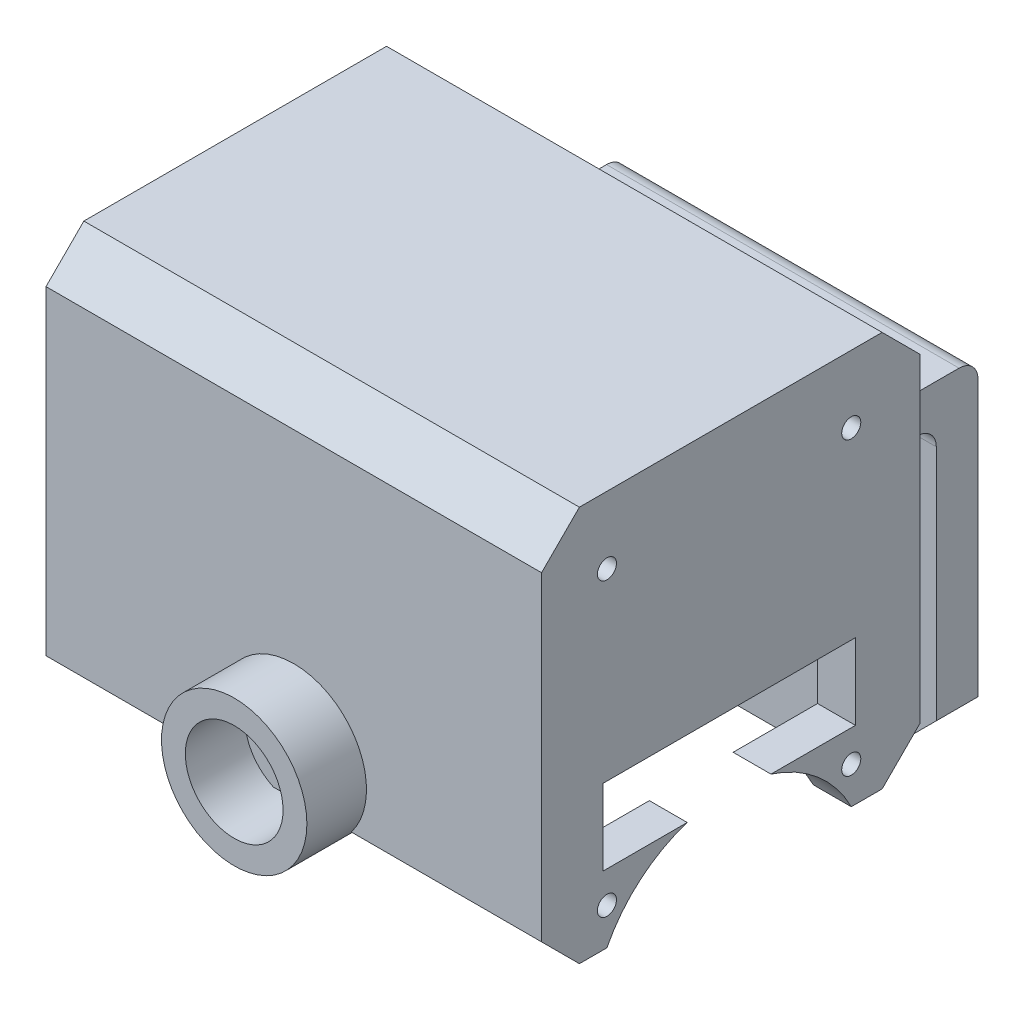
SolidWorks part; units mm, degrees
material "PLA"
ref_plane "Front Plane" through (0, 0, 0) normal (0, 0, 1) x (1, 0, 0)
ref_plane "Top Plane" through (0, 0, 0) normal (0, 1, 0) x (1, 0, 0)
ref_plane "Right Plane" through (0, 0, 0) normal (1, 0, 0) x (0, 0, -1)
sketch "Sketch1" plane through (0, 0, 0) normal (1, 0, 0) x (0, 0, -1)
  line L1 (0, 0) -> (25, 0)
  line L2 (0, 0) -> (0, 30)
  line L3 (0, 30) -> (25, 30)
  line L4 (25, 0) -> (25, 30)
  dimension "D1" = 30
  dimension "D2" = 25
extrude "Boss-Extrude1" add sketch "Sketch1" along normal blind 3.175
sketch "Sketch2" plane through (0, 0, 0) normal (-1, 0, 0) x (0, 0, 1)
  line L1 (-25, 30) -> (0, 30)
  line L2 (-25, 30) -> (-25, 33.175)
  line L3 (-25, 33.175) -> (0, 33.175)
  line L4 (0, 30) -> (0, 33.175)
  dimension "D1" = 3.175
extrude "Boss-Extrude2" add sketch "Sketch2" against normal blind 41.58
sketch "Sketch3" plane through (0, 30, 0) normal (0, -1, 0) x (1, 0, 0)
  line L0 (41.58, 0) -> (3.175, 0) construction
  line L1 (41.58, -25) -> (38.405, -25)
  line L2 (41.58, -25) -> (41.58, 0)
  line L3 (41.58, 0) -> (38.405, 0)
  line L4 (38.405, -25) -> (38.405, 0)
  dimension "D1" = 3.175
extrude "Boss-Extrude3" add sketch "Sketch3" along normal up to surface (30 mm away) up to face at (1.5875, 0, -12.5)
sketch "Sketch4" plane through (0, 0, 0) normal (-1, 0, 0) x (0, 0, 1)
  circle A0 centre (-12.36, -5.21) radius 11.5
  dimension "D1" = 23
extrude "Cut-Extrude1" cut sketch "Sketch4" against normal up to next
sketch "Sketch5" plane through (0, 0, 0) normal (-1, 0, 0) x (0, 0, 1)
  circle A0 centre (-22.61, 3.09) radius 0.8
  circle A1 centre (-22.61, 23.79) radius 0.8
  circle A2 centre (-2.11, 23.79) radius 0.8
  circle A3 centre (-2.11, 3.09) radius 0.8
extrude "Cut-Extrude2" cut sketch "Sketch5" against normal up to next
sketch "Sketch6" plane through (41.58, 0, 0) normal (1, 0, 0) x (0, 0, -1)
  line L1 (1.76, 5.74) -> (22.96, 5.74)
  line L2 (1.76, 5.74) -> (1.76, 12.115)
  line L3 (1.76, 12.115) -> (22.96, 12.115)
  line L4 (22.96, 5.74) -> (22.96, 12.115)
  circle A0 centre (2.11, 3.09) radius 0.8
  circle A1 centre (22.61, 3.09) radius 0.8
  circle A2 centre (22.61, 27.54) radius 0.7999
  circle A3 centre (2.11, 27.54) radius 0.8
extrude "Cut-Extrude3" cut sketch "Sketch6" against normal up to next
sketch "Sketch7" plane through (41.58, 0, 0) normal (1, 0, 0) x (0, 0, -1)
  circle A0 centre (12.36, -5.21) radius 11.5
  dimension "D1" = 23
extrude "Cut-Extrude4" cut sketch "Sketch7" against normal up to next
sketch "Sketch8" plane through (0, 0, 0) normal (0, 0, 1) x (1, 0, 0)
  line L8 (0, 33.175) -> (0, 0)
  line L9 (0, 0) -> (3.175, 0)
  line L10 (3.175, 0) -> (3.175, 30)
  line L11 (3.175, 30) -> (38.405, 30)
  line L12 (38.405, 30) -> (38.405, 0)
  line L13 (38.405, 0) -> (41.58, 0)
  line L14 (41.58, 0) -> (41.58, 33.175)
  line L15 (41.58, 33.175) -> (0, 33.175)
  line L16 (0, 33.175) -> (0, 0)
  line L17 (0, 0) -> (3.175, 0)
  line L18 (3.175, 0) -> (3.175, 30)
  line L19 (3.175, 30) -> (38.405, 30)
  line L20 (38.405, 30) -> (38.405, 0)
  line L21 (38.405, 0) -> (41.58, 0)
  line L22 (41.58, 0) -> (41.58, 33.175)
  line L23 (41.58, 33.175) -> (0, 33.175)
  dimension "D1" = 0
extrude "Boss-Extrude4" add sketch "Sketch8" along normal blind 0.2
sketch "Sketch9" plane through (0, 0, 0.2) normal (0, 0, 1) x (1, 0, 0)
  line L1 (0, 0) -> (41.58, 0)
  line L2 (0, 0) -> (0, 33.175)
  line L3 (0, 33.175) -> (41.58, 33.175)
  line L4 (41.58, 0) -> (41.58, 33.175)
extrude "Boss-Extrude5" add sketch "Sketch9" along normal blind 3.175
sketch "Sketch10" plane through (0, 0, -25) normal (0, 0, -1) x (-1, 0, 0)
  line L8 (0, 0) -> (0, 33.175)
  line L9 (0, 33.175) -> (-41.58, 33.175)
  line L10 (-41.58, 33.175) -> (-41.58, 0)
  line L11 (-41.58, 0) -> (-38.405, 0)
  line L12 (-38.405, 0) -> (-38.405, 30)
  line L13 (-38.405, 30) -> (-3.175, 30)
  line L14 (-3.175, 30) -> (-3.175, 0)
  line L15 (-3.175, 0) -> (0, 0)
  line L16 (0, 0) -> (0, 33.175)
  line L17 (0, 33.175) -> (-41.58, 33.175)
  line L18 (-41.58, 33.175) -> (-41.58, 0)
  line L19 (-41.58, 0) -> (-38.405, 0)
  line L20 (-38.405, 0) -> (-38.405, 30)
  line L21 (-38.405, 30) -> (-3.175, 30)
  line L22 (-3.175, 30) -> (-3.175, 0)
  line L23 (-3.175, 0) -> (0, 0)
  dimension "D1" = 0
extrude "Boss-Extrude6" add sketch "Sketch10" along normal blind 0.2
sketch "Sketch11" plane through (0, 0, -25.2) normal (0, 0, -1) x (-1, 0, 0)
  line L1 (-41.58, 0) -> (0, 0)
  line L2 (-41.58, 0) -> (-41.58, 33.175)
  line L3 (-41.58, 33.175) -> (0, 33.175)
  line L4 (0, 0) -> (0, 33.175)
extrude "Boss-Extrude7" add sketch "Sketch11" along normal blind 3.175
chamfer "Chamfer1" distance 3.175 angle 45 2 edges at (20.79, 33.175, 3.375) (20.79, 33.175, -28.375)
chamfer "Chamfer2" distance 3.175 angle 45 2 edges at (20.79, 0, 3.375) (20.79, 0, -28.375)
sketch "Sketch13" plane through (0, 0, -28.375) normal (0, 0, -1) x (-1, 0, 0)
  line L0 (0, 3.175) -> (0, 30) construction
  line L1 (-35.58, 18.175) -> (-6, 18.175)
  line L3 (-35.58, 21.35) -> (-6, 21.35)
  line L5 (-35.58, 21.35) -> (-35.58, 18.175)
  line L6 (-6, 21.35) -> (-6, 18.175)
  line L7 (-41.58, 30) -> (-41.58, 3.175) construction
  line L9 (-41.58, 3.175) -> (0, 3.175) construction
  dimension "D1" = 3.175
  dimension "D2" = 6
  dimension "D3" = 6
  dimension "D4" = 15
extrude "Boss-Extrude8" add sketch "Sketch13" along normal blind 7.695
sketch "Sketch14" plane through (0, 18.175, 0) normal (0, -1, 0) x (1, 0, 0)
  line L0 (35.58, -35.745) -> (35.58, -39.2524) construction
  line L1 (-0.7092, -39.245) -> (9.3147, -39.245) construction
  line L7 (6, -35.745) -> (6, -39.245)
  line L8 (6, -39.245) -> (35.58, -39.245)
  line L9 (35.58, -35.745) -> (35.58, -39.245)
  line L11 (35.58, -36.07) -> (6, -36.07) construction
  line L12 (6, -35.745) -> (35.58, -35.745)
  dimension "D1" = 3.5
  dimension "D2" = 3.175
  dimension "D3" = 3.5
extrude "Boss-Extrude9" add sketch "Sketch14" against normal up to surface and the other way blind 25 up to face at (20.79, 21.35, -32.2225)
chamfer "Chamfer3" distance 3.5 angle 45 2 edges at (35.58, -6.825, -37.495) (6, -6.825, -37.495)
fillet "Fillet1" radius 1.5875 2 edges at (20.79, 21.35, -39.245) (20.79, 18.175, -35.745)
fillet "Fillet2" radius 1.5875 1 edges at (20.79, 21.35, -28.375)
sketch "Sketch16" plane through (0, 0, -39.245) normal (0, 0, -1) x (-1, 0, 0)
  line L0 (-20.79, 19.7625) -> (-20.79, 6.9025) construction
  line L1 (-6, 19.7625) -> (-35.58, 19.7625) construction
  circle A0 centre (-20.79, 6.9025) radius 7.1
  dimension "D2" = 14.2
  dimension "D1" = 12.86
extrude "Cut-Extrude5" cut sketch "Sketch16" against normal up to next
sketch "Sketch20" plane through (0, 0, -35.745) normal (0, 0, 1) x (1, 0, 0)
  circle A0 centre (20.79, 6.9025) radius 7.1 construction
  circle A1 centre (20.79, 6.9025) radius 7.1 construction
  circle A2 centre (20.79, 6.9025) radius 4.1
  circle A3 centre (20.79, 6.9025) radius 8
  dimension "D1" = 8.2
  dimension "D2" = 16
extrude "Boss-Extrude11" add sketch "Sketch20" along normal blind 5
sketch "Sketch21" plane through (0, -6.825, 0) normal (0, -1, 0) x (1, 0, 0)
  line L0 (20.79, -30.745) -> (20.79, -35.745) construction
  line L1 (28.79, -30.745) -> (12.79, -30.745) construction
  line L2 (32.08, -35.745) -> (9.5, -35.745) construction
  circle A0 centre (20.79, -33.245) radius 1.025
  dimension "D1" = 2.05
extrude "Cut-Extrude6" cut sketch "Sketch21" against normal up to surface (25 mm away)
sketch "Sketch23" plane through (0, 0, 3.375) normal (0, 0, 1) x (1, 0, 0)
  circle A2 centre (20.79, 6.9025) radius 4.1
  circle A4 centre (20.79, 6.9025) radius 6.1
  dimension "D1" = 8.2
  dimension "D2" = 12.2
extrude "Boss-Extrude12" add sketch "Sketch23" against normal blind 1.2 and the other way blind 5
chamfer "Chamfer4" distance 1.5 angle 45 3 edges at (6, 20.5563, -28.375) (35.58, 20.5563, -28.375) (20.79, 18.175, -28.375)
sketch "Sketch24" plane through (0, 0, -39.245) normal (0, 0, -1) x (-1, 0, 0)
  circle A0 centre (-20.79, 6.9025) radius 10
  circle A1 centre (-20.79, 6.9025) radius 11.5
  dimension "D1" = 20
  dimension "D2" = 1.5
extrude "Boss-Extrude13" add sketch "Sketch24" along normal blind 1.8
